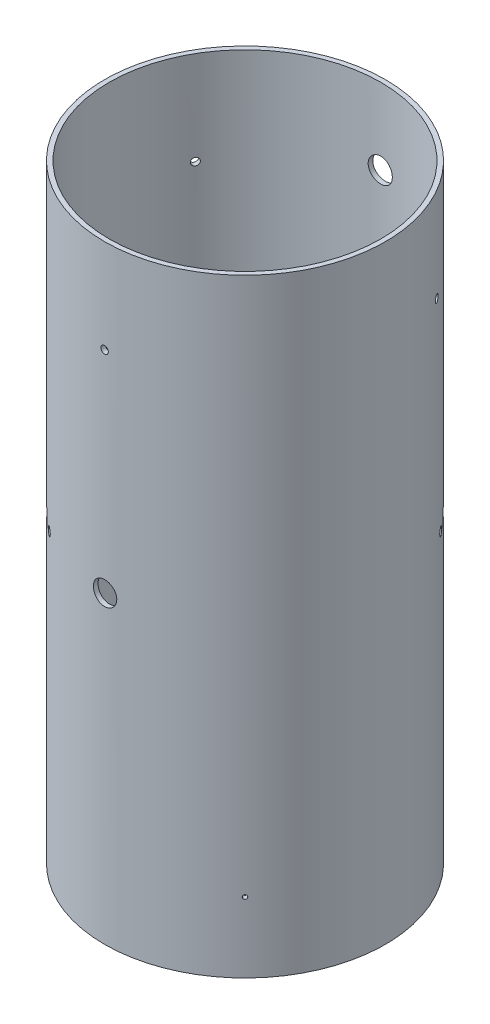
SolidWorks part; units mm, degrees
material "A-Glass Fiber"
ref_plane "Front Plane" through (0, 0, 0) normal (0, 0, 1) x (1, 0, 0)
ref_plane "Top Plane" through (0, 0, 0) normal (0, 1, 0) x (1, 0, 0)
ref_plane "Right Plane" through (0, 0, 0) normal (1, 0, 0) x (0, 0, -1)
sketch "Sketch1" plane through (0, 0, 0) normal (0, 1, 0) x (1, 0, 0)
  circle A0 centre (0, 0) radius 76.1746
  circle A1 centre (0, 0) radius 73.66
  dimension "D1" = 152.3492
  dimension "D2" = 147.32
extrude "Boss-Extrude1" add sketch "Sketch1" along normal blind 330.2
sketch "Sketch4" plane through (0, 0, 0) normal (0, 0, 1) x (1, 0, 0)
  line L0 (-76.1746, 0) -> (76.1746, 0) construction
  line L1 (76.1746, 330.2) -> (-76.1746, 330.2) construction
  line L2 (0, 330.2) -> (0, 0) construction
  line L3 (73.66, 330.2) -> (-73.66, 330.2) construction
  point P0 (0, 41.275)
  point P3 (0, 288.925)
  dimension "D1" = 41.275
  dimension "D2" = 41.275
hole_wizard "1/2 Clearance Hole5" positions "Sketch16" profile "Sketch17" hole size "1/2" standard "ANSI Inch"
sketch "Sketch16" plane through (0, 0, 0) normal (0, 0, 1) x (1, 0, 0)
  point P0 (0, 288.925)
sketch "Sketch17" plane through (0, 288.925, 0) normal (1, 0, 0) x (0, -1, 0)
  line L0 (0, 0) -> (0, 80.1345)
  line L1 (0, 80.1345) -> (6.5481, 76.2)
  line L2 (6.5481, 76.2) -> (6.5481, 0)
  line L5 (6.5481, 0) -> (0, 0)
  line L10 (0, 80.1345) -> (-6.5481, 76.2) construction
  line L11 (0, -6.35) -> (0, 107.95) construction
  dimension "Hole Dia." = 13.0962
  dimension "Hole Depth" = 76.2
  dimension "Drill Angle" = 118
sketch "Sketch27" plane through (0, 0, 0) normal (0, 0, 1) x (1, 0, 0)
  line L0 (0, 330.2) -> (0, 0) construction
  line L1 (-76.1746, 0) -> (76.1746, 0) construction
  circle A0 centre (0, 165.1) radius 6.35
  dimension "D1" = 12.7
  dimension "D2" = 165.1
extrude "Cut-Extrude1" cut sketch "Sketch27" against normal through all both and the other way through all
ref_plane "Plane1" through (0, 0, 0) normal (-0.7071, 0, 0.7071) x (0.7071, 0, 0.7071)
sketch "Sketch30" plane through (0, 0, 0) normal (-0.7071, 0, 0.7071) x (0.7071, 0, 0.7071)
  line L0 (0, 330.2) -> (0, 0) construction
  line L1 (4.953, 160.147) -> (-4.953, 160.147)
  line L2 (4.953, 160.147) -> (4.953, 170.053)
  line L3 (4.953, 170.053) -> (-4.953, 170.053)
  line L4 (-4.953, 160.147) -> (-4.953, 170.053)
  line L5 (4.953, 160.147) -> (-4.953, 170.053) construction
  line L6 (4.953, 170.053) -> (-4.953, 160.147) construction
  line L7 (-76.1746, 0) -> (76.1746, 0) construction
  circle A0 centre (-12.7, 165.1) radius 2.1831
  circle A1 centre (12.7, 165.1) radius 2.1831
  point P0 (0, 165.1)
  dimension "D3" = 4.3663
  dimension "D4" = 4.3663
  dimension "D1" = 9.906
  dimension "D2" = 9.906
  dimension "D5" = 12.7
  dimension "D6" = 12.7
  dimension "D7" = 165.1
extrude "Cut-Extrude2" cut sketch "Sketch30" against normal through all both and the other way through all
sketch "Sketch23" plane through (0, 0, 0) normal (-0.7071, 0, 0.7071) x (0.7071, 0, 0.7071)
  line L0 (0, 0) -> (0, 330.2) construction
  line L1 (73.66, 330.2) -> (-73.66, 330.2) construction
  line L2 (-76.1746, 165.1) -> (76.1746, 165.1) construction
  line L3 (76.1746, 0) -> (76.1746, 330.2) construction
  circle A1 centre (0, 38.1) radius 1.0922
  point P12 (0, 165.1)
  dimension "D2" = 127
extrude "Shear Scrrews" cut sketch "Sketch23" against normal through all
pattern_circular "CirPattern1" count 4 over 360 about axis through (0, 330.2, 0) along (0, -1, 0) of "Shear Scrrews"
hole_wizard "Ø4.0 (4) Diameter Hole1" positions "Sketch24" profile "Sketch25" hole size "Ø4.0" standard "ANSI Metric"
sketch "Sketch24" plane through (0, 0, 0) normal (0, 0, 1) x (1, 0, 0)
  line L0 (76.1746, 330.2) -> (-76.1746, 330.2) construction
  point P0 (0, 279.4)
  dimension "D1" = 50.8
sketch "Sketch25" plane through (0, 279.4, 0) normal (1, 0, 0) x (0, 1, 0)
  line L0 (0, 0) -> (0, 90.1017)
  line L1 (0, 90.1017) -> (2, 88.9)
  line L2 (2, 88.9) -> (2, 0)
  line L5 (2, 0) -> (0, 0)
  line L10 (0, 90.1017) -> (-2, 88.9) construction
  line L11 (0, -6.35) -> (0, 107.95) construction
  dimension "Hole Dia." = 4
  dimension "Hole Depth" = 88.9
  dimension "Drill Angle" = 118
pattern_circular "CirPattern2" count 3 over 360 about axis through (0, 330.2, 0) along (0, 1, 0) of "Ø4.0 (4) Diameter Hole1"
equation "\"Mid_Coupler_Length\" = 13in"
equation "\"D1@Boss-Extrude1\"=\"Mid_Coupler_Length\""
equation "\"Shear_Screw_Coupler_Location\" = 4.5in"
equation "\"Shear_Screw_Diameter\" = 0.086in"
equation "\"D2@Sketch23\"=\"Shear_Screw_Coupler_Location\"+0.5"
equation "\"Mid_Tube_Length\"= 1in"
equation "\"Bodytube_OD\" = 6.17in"
equation "\"Bodytube_ID\" = 5.998in"
equation "\"Camera_Cutout_Width\"=10mm"
equation "\"Camera_Cutout_Height\"=7mm"
equation "\"Fwd_Tube_Length\" = 40in"
equation "\"BKHD_Screw_Diam\"= 3.5mm"
equation "\"Fwd_BKHD_From_Top\" = 18in"
equation "\"Motor_OD\" = 4in"
equation "\"Aft_Section_Length\"= 36in"
equation "\"AB_Coupler_OD_Length\"= 1in"
equation "\"AB_Coupling_Section_Length\"= 0.375in"
equation "\"AB_Coupler_Length\"= \"AB_Coupler_OD_Length\" + \"AB_Coupling_Section_Length\" * 2"
equation "\"Cutout_Angle\" = 80"
equation "\"AB_Paddle_Height\" = 0.375in"
equation "\"AB_Coupler_Num_Screws\"= 4"
equation "\"AB_BKHD_Thickness\" = 0.375in"
equation "\"AB_Mount_From_Bottom\" = 23.175in"
equation "\"Num_Cutouts\" = 3"
equation "\"AB_Coupler_OD\"= 6.17in"
equation "\"AB_Coupler_ID\"= 5.75in"
equation "\"AB_Coupler_Surface_Diameter\"= 5.998in"
equation "\"AB_Coupling_Screw_Diameter\"= 0.15748in"
equation "\"AB_Central_Bushing_Length\" = .4724in"
equation "\"Lead_Screw_Dist\" = 3.4in"
equation "\"Lead_Screw_Diam\" = 0.386in"
equation "\"Lead_Screw_Length\" = (\"Mid_Coupler_Length\" + 2*0.375in + 2*.75in)"
equation "\"Paddle_Pin_Offset\" = .25in"
equation "\"Paddle_Pin_Radius\" = 2.25in"
equation "\"SS_Paddle_Pin_Radius\" = 2.25*0.66in"
equation "\"Paddle_Gear_OD\" = 3.2in"
equation "\"Drive_Gear_OD\" = 1.7in"
equation "\"Fin_Thickness\"= .118in"
equation "\"Guiderail_Cutout_Diameter\"= 1.5in"
equation "\"DB9_Hole_Dist\" = 25mm"
equation "\"DB9_Relief_Width\" = 0.47in"
equation "\"DB9_Relief_Hole_Offset\" = 0.09in"
equation "\"Airbrakes_Wire_Hole_Dia\" = .25in"
equation "\"Airbrakes_Wire_Hole_Dist\" = 1.1in"
equation "\"Servo_Gear_Offset\" = 0.5in"
equation "\"FWD_Shear_Screw_Dist\" = 1.5in"
equation "\"Camera_Screw_Dia\" = 0.216535"
equation "\"Camera_Hole_Angle\" = atn ( 2 / 3 * tan ( 12.5deg ) )"
equation "\"D1@Sketch26\"=\"Camera_Cutout_Height\""
equation "\"D2@Sketch26\"=\"Camera_Cutout_Width\""
equation "\"D3@Sketch26\"=6.125"
equation "\"D1@Sketch28\"=\"Camera_Screw_Dia\""
equation "\"D2@CirPattern3\"=\"Camera_Hole_Angle\""
equation "\"D1@Sketch29\"=\"Camera_Screw_Dia\""
equation "\"D2@CirPattern4\"=\"Camera_Hole_Angle\""
equation "\"Coupler_OD\" = 5.998"
equation "\"D1@Sketch1\"=\"Coupler_OD\""
equation "\"Coupler_ID\" = 5.8"
equation "\"D2@Sketch1\"=\"Coupler_ID\""
